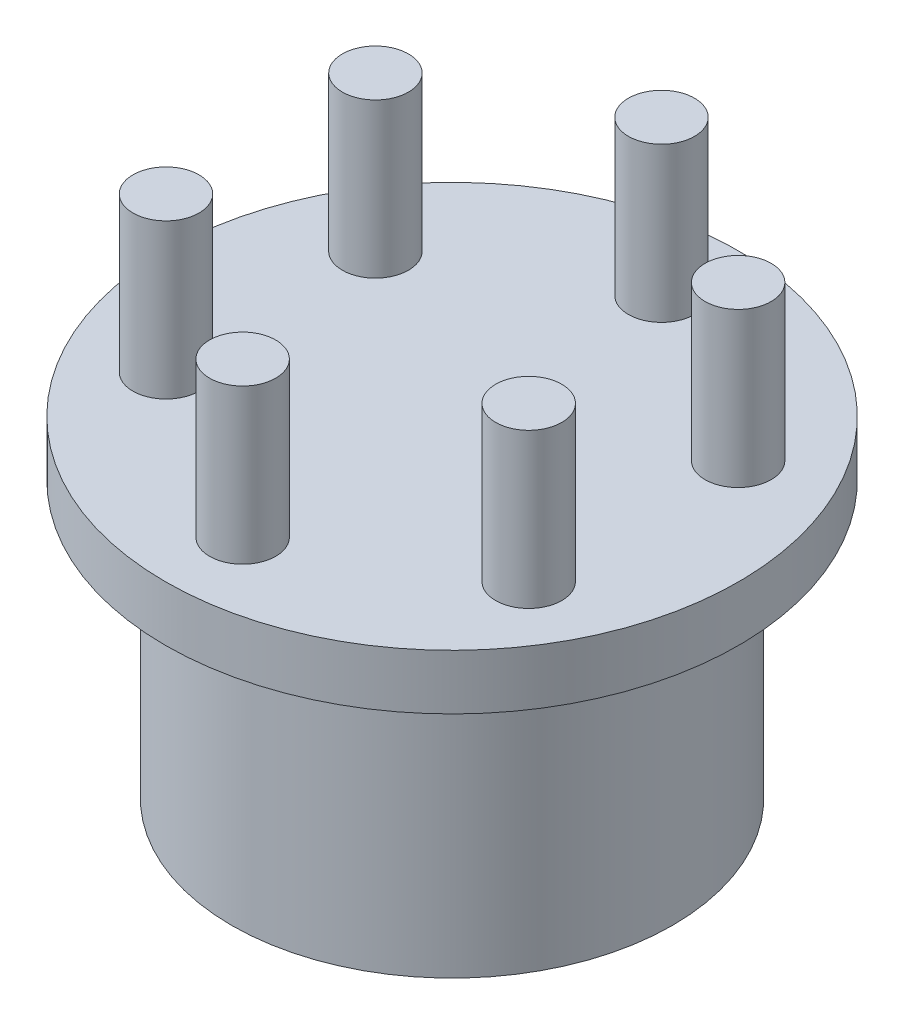
SolidWorks part; units mm, degrees
ref_plane "Front Plane" through (0, 0, 0) normal (0, 0, 1) x (1, 0, 0)
ref_plane "Top Plane" through (0, 0, 0) normal (0, 1, 0) x (1, 0, 0)
ref_plane "Right Plane" through (0, 0, 0) normal (1, 0, 0) x (0, 0, -1)
sketch "Sketch1" plane through (0, 0, 0) normal (0, 1, 0) x (1, 0, 0)
  circle A0 centre (0, 0) radius 26
  point P18 (0, 0)
  dimension "D1" = 52
extrude "Boss-Extrude1" add sketch "Sketch1" along normal blind 5 contours A0
sketch "Sketch2" plane through (0, 5, 0) normal (0, 1, 0) x (1, 0, 0)
  line L0 (0, 0) -> (0, 19) construction
  circle A0 centre (0, 0) radius 11.25
  circle A1 centre (0, 19) radius 3
  circle A2 centre (16.4545, 9.5) radius 3
  circle A3 centre (16.4545, -9.5) radius 3
  circle A4 centre (0, -19) radius 3
  circle A5 centre (-16.4545, -9.5) radius 3
  circle A6 centre (-16.4545, 9.5) radius 3
  dimension "D1" = 22.5
  dimension "D2" = 6
  dimension "D5" = 19
  dimension "D4" = 6
extrude "Boss-Extrude3" add sketch "Sketch2" along normal blind 14 contours A3 | A2 | A1 | A6 | A5 | A4 region at (0, 5, -19) region at (16.4545, 5, -9.5) region at (16.4545, 5, 9.5) region at (0, 5, 19) region at (-16.4545, 5, 9.5) region at (-16.4545, 5, -9.5)
sketch "Sketch4" plane through (0, 5, 0) normal (0, 1, 0) x (1, 0, 0)
  circle A0 centre (0, 0) radius 20
  dimension "D1" = 40
extrude "Boss-Extrude4" add sketch "Sketch4" against normal blind 30 contours A0
sketch "Sketch10" plane through (0, -25, 0) normal (0, -1, 0) x (1, 0, 0)
  line L0 (16.5, 4) -> (16.5, -4)
  line L1 (-4, 16.5) -> (4, 16.5)
  line L2 (-4, 16.5) -> (-4, 11.8427)
  line L4 (4, 16.5) -> (4, 11.8427)
  line L5 (-4, 16.5) -> (4, 8.5) construction
  line L6 (0, 12.5) -> (4, 16.5) construction
  line L7 (16.5, 4) -> (11.8427, 4)
  line L8 (16.5, -4) -> (11.8427, -4)
  line L9 (4, -16.5) -> (-4, -16.5)
  line L10 (4, -16.5) -> (4, -11.8427)
  line L11 (-4, -16.5) -> (-4, -11.8427)
  line L12 (-16.5, -4) -> (-16.5, 4)
  line L13 (-16.5, -4) -> (-11.8427, -4)
  line L14 (-16.5, 4) -> (-11.8427, 4)
  arc A0 (-4, 11.8427) -> (-11.8427, 4) centre (0, 0) ccw
  arc A1 (11.8427, 4) -> (4, 11.8427) centre (0, 0) ccw
  arc A2 (4, -11.8427) -> (11.8427, -4) centre (0, 0) ccw
  arc A3 (-11.8427, -4) -> (-4, -11.8427) centre (0, 0) ccw
  point P3 (0, 12.5)
  point P25 (0, 0)
  dimension "D1" = 8
  dimension "D3" = 25
  dimension "D2" = 8
  dimension "D4" = 4
extrude "Cut-Extrude3" cut sketch "Sketch10" against normal blind 20 contours A0 L14 L12 L13 A3 L11 L9 L10 A2 L8 L0 L7 A1 L4 L1 L2
